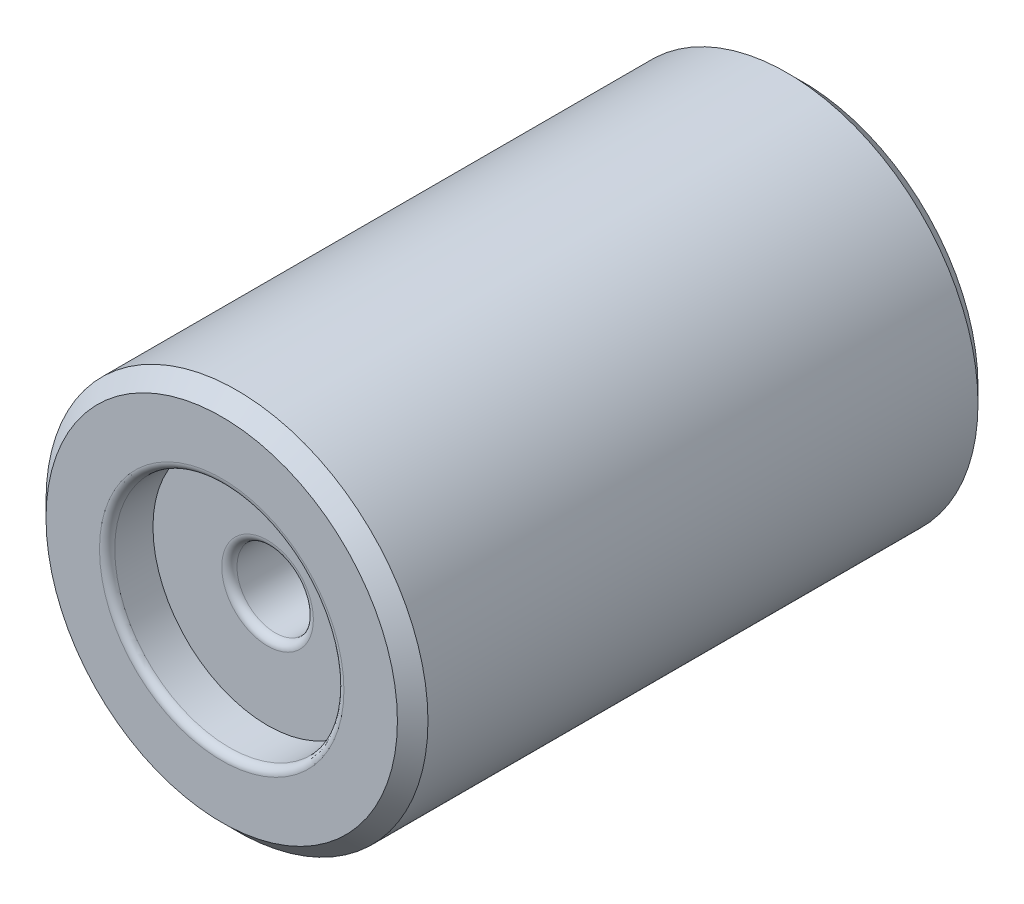
SolidWorks part; units mm, degrees
material "moto_grey"
ref_plane "Front Plane" through (0, 0, 0) normal (0, 0, 1) x (1, 0, 0)
ref_plane "Top Plane" through (0, 0, 0) normal (0, 1, 0) x (1, 0, 0)
ref_plane "Right Plane" through (0, 0, 0) normal (1, 0, 0) x (0, 0, -1)
sketch "Sketch1" plane through (0, 0, 0) normal (0, 0, 1) x (1, 0, 0)
  circle A0 centre (0, 0) radius 12.5
  circle A1 centre (0, 0) radius 7.5
  circle A2 centre (0, 0) radius 2.5
  dimension "D1" = 25
  dimension "D2" = 15
  dimension "D3" = 5
extrude "Boss-Extrude2" add sketch "Sketch1" along normal mid plane 38 contours A0 A1 region at (-12.1464, 0, 0)
extrude "Boss-Extrude3" add sketch "Sketch1<4>" along normal mid plane 32 contours A1 A2 region at (-7.2879, 0, 0)
sketch "Sketch1<4>" plane through (0, 0, 0) normal (0, 0, 1) x (1, 0, 0) same geometry as "Sketch1"
chamfer "Chamfer1" distance 1 angle 45 2 edges at (12.5, 0, 19) (12.5, 0, -19)
fillet "Fillet1" radius 0.5 4 edges at (2.5, 0, -16) (7.5, 0, -16) (7.5, 0, -19) (7.5, 0, 19)
fillet "Fillet2" radius 0.5 1 edges at (2.5, 0, 16)
